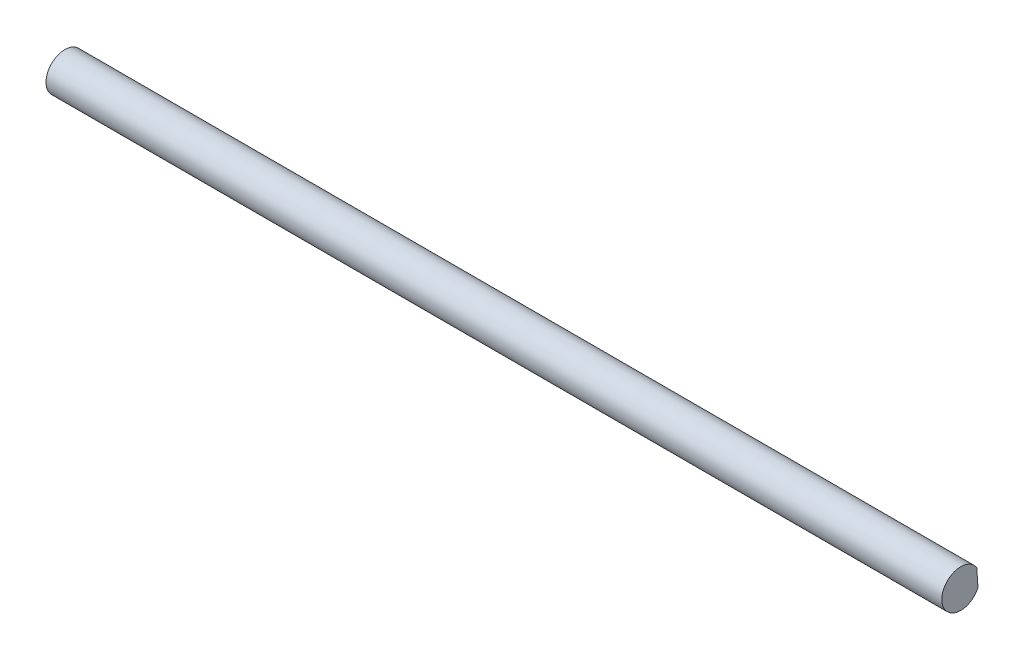
SolidWorks part; units mm, degrees
ref_plane "Plan de face" through (0, 0, 0) normal (0, 0, 1) x (1, 0, 0)
ref_plane "Plan de dessus" through (0, 0, 0) normal (0, 1, 0) x (1, 0, 0)
ref_plane "Plan de droite" through (0, 0, 0) normal (1, 0, 0) x (0, 0, -1)
sketch "Esquisse1" plane through (0, 0, 0) normal (1, 0, 0) x (0, 0, -1)
  line L1 (2.8915, -1.3114) -> (2.6832, 1.6974)
  arc A0 (2.6832, 1.6974) -> (2.8915, -1.3114) centre (0, 0) ccw
  point P1 (0, 0)
  point P3 (2.8915, -1.3114)
  point P6 (0, 0)
  point P7 (0, 0)
  dimension "D1" = 6.35
  dimension "D2" = 2.794
extrude "Boss.-Extru.1" add sketch "Esquisse1" along normal blind 150
